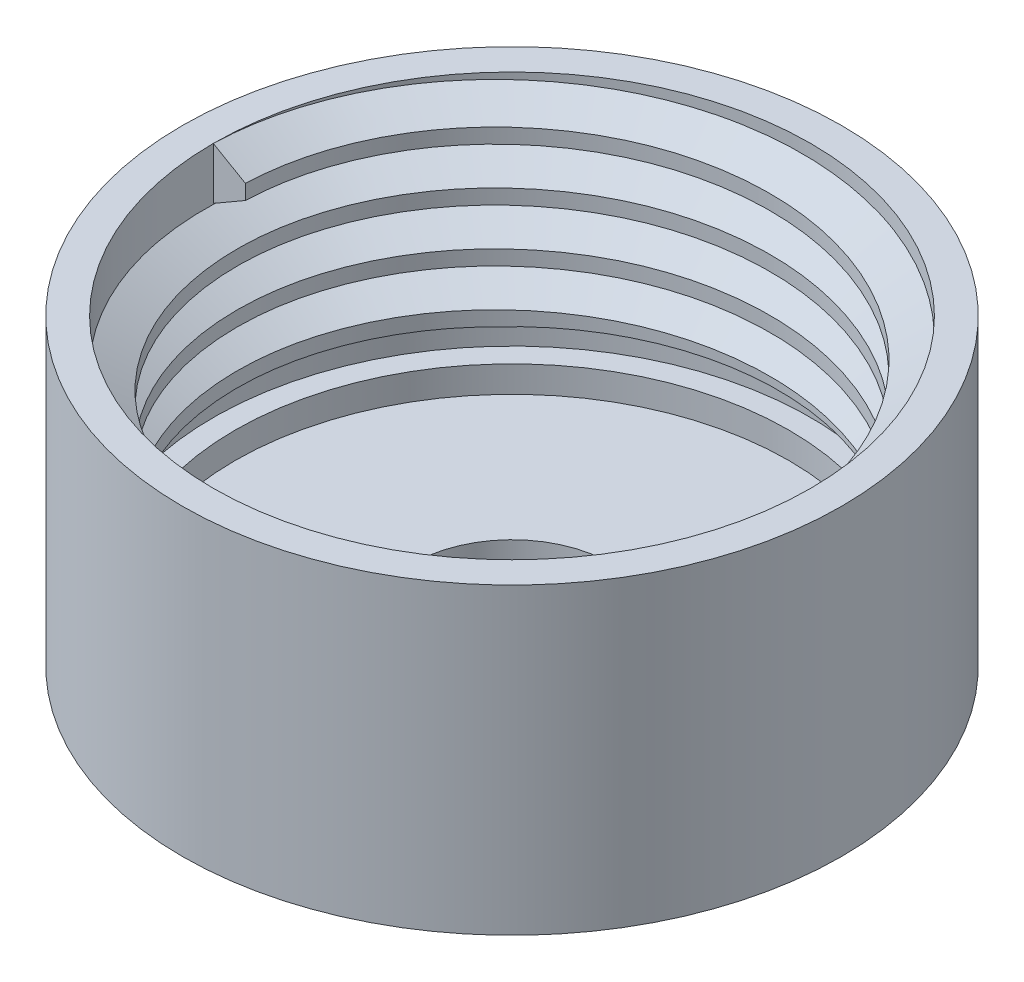
SolidWorks part; units mm, degrees
ref_plane "Front Plane" through (0, 0, 0) normal (0, 0, 1) x (1, 0, 0)
ref_plane "Top Plane" through (0, 0, 0) normal (0, 1, 0) x (1, 0, 0)
ref_plane "Right Plane" through (0, 0, 0) normal (1, 0, 0) x (0, 0, -1)
sketch "Sketch1" plane through (0, 0, 0) normal (0, 1, 0) x (1, 0, 0)
  circle A0 centre (0, 0) radius 25
  circle A1 centre (0, 0) radius 7.5
  dimension "D1" = 15
  dimension "D2" = 50
extrude "Boss-Extrude1" add sketch "Sketch1" along normal blind 23
sketch "Sketch2" plane through (0, 23, 0) normal (0, 1, 0) x (1, 0, 0)
  circle A0 centre (0, 0) radius 21
  dimension "D1" = 42
extrude "Cut-Extrude1" cut sketch "Sketch2" against normal blind 20
sketch "Sketch3" plane through (0, 23, 0) normal (0, 1, 0) x (1, 0, 0)
  circle A0 centre (0, 0) radius 22.65
  dimension "D1" = 45.3
extrude "Cut-Extrude2" cut sketch "Sketch3" against normal blind 18
thread "Thread1" pitch 4.5 method extrude profile "Thread Profile2" start angle 0, offset 0, length 15, pitch 4, diameter 45.3
ref_plane "Plane2" through (-22.65, 23, 0) normal (0, 0, 1) x (-1, 0, 0)
sketch "Thread Profile2" plane through (-22.65, 23, 0) normal (0, 0, 1) x (-1, 0, 0)
  line L0 (0, 0) -> (0, 4.5) construction
  line L11 (0, 0) -> (0, 3.9375)
  line L12 (0, 3.9375) -> (-2.4357, 2.5312)
  line L13 (-2.4357, 2.5312) -> (-2.4357, 1.4062)
  line L15 (-2.4357, 1.4062) -> (0, 0)
  line L17 (-2.4357, 1.9687) -> (0, 1.9687) construction
  point P2 (0, 0)
  dimension "Pitch" = 4.5
  dimension "Profile_Angle" = 60
  dimension "Profile_Land" = 1.125
  dimension "Profile_Height" = 2.4357
sketch "Sketch11" plane through (0, 5, 0) normal (0, 1, 0) x (1, 0, 0)
  circle A0 centre (0, 0) radius 22.65
  dimension "D1" = 45.3
extrude "Cut-Extrude3" cut sketch "Sketch11" along normal blind 3
